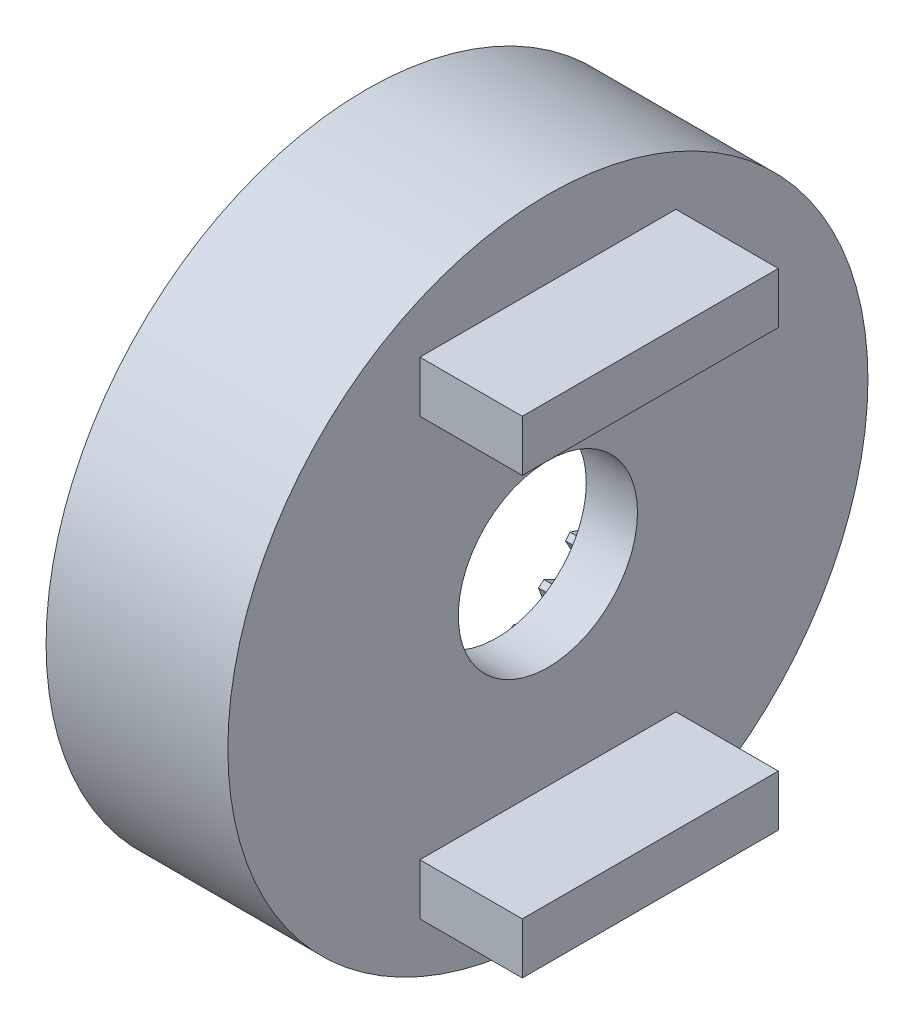
SolidWorks part; units mm, degrees
ref_plane "Plane1" through (0, 0, 0) normal (0, 0, 1) x (1, 0, 0)
ref_plane "Plane2" through (0, 0, 0) normal (0, 1, 0) x (1, 0, 0)
ref_plane "Plane3" through (0, 0, 0) normal (1, 0, 0) x (0, 0, -1)
other "Configuration Table"
sketch "HoldingSke" plane through (0, 0, 0) normal (0, 1, 0) x (1, 0, 0)
  line L0 (0, 0) -> (1.4627, -1.364)
  line L1 (-15, 0) -> (100, 0) construction
  line L2 (0, 0) -> (-2.1039, 2.3779)
  line L3 (0, 0) -> (-11.863, 4.5341)
  line L4 (0, 0) -> (6.316, 5.8897)
  line L5 (0, 0) -> (-23.7986, -8.8762)
  line L6 (0, 0) -> (-10.5278, -7.1032)
  line L7 (-2.1039, 2.3779) -> (3.3635, 27.1825)
  line L8 (-76.2, 2.8779) -> (-54.61, 2.8779)
  line L9 (-71.009, 38.7566) -> (-53.1078, 45.2721)
  line L10 (-76.2, 71.12) -> (104.1128, 71.12)
  line L11 (0, 0) -> (-2, 0)
  line L12 (-76.2, 101.6) -> (-76.181, 101.6)
  line L13 (24.9733, 27.94) -> (52.9518, 28.4284)
  line L14 (24.9733, 27.94) -> (24.9743, 27.94)
  line L15 (24.9733, 27.94) -> (100.4006, 29.5858)
  circle A0 centre (0, 0) radius 12.5
  circle A1 centre (0, 0) radius 12.7
  circle A2 centre (0, 0) radius 12.7
  dimension "Num_teeth" = 43
  dimension "Pitch_radius" = 180.3128
  dimension "Width" = 2
  dimension "Diameter" = 25
sketch "BasProSke" plane through (0, 0, 0) normal (0, 1, 0) x (1, 0, 0)
  line L0 (-10, 0) -> (60, 0) construction
  line L1 (0, 10.25) -> (0, 12.5)
  line L2 (0, 10.25) -> (5.1, 10.25)
  line L3 (5.1, 10.25) -> (5.1, 12.5)
  line L4 (5.1, 12.5) -> (0, 12.5)
  dimension "Thickness" = 5.1
  dimension "Diameter" = 25
revolve "Base-Revolve" add sketch "BasProSke" angle 360 about L0
sketch "TooCutSke" plane through (0, 0, 0) normal (1, 0, 0) x (0, 0, -1)
  line L3 (0.4401, 10.741) -> (0.4401, 53.6633) construction
  line L4 (0, 0) -> (0, 59.563) construction
  line L5 (0, 0) -> (-4.9876, 68.1452) construction
  line L6 (-4.5651, 8.7817) -> (37.0782, 11.8296) construction
  circle A0 centre (0, 0) radius 10.75 construction
  circle A1 centre (0, 0) radius 11.376 construction
  circle A2 centre (0, 0) radius 9.0915 construction
  circle A3 centre (0, 0) radius 10.2246 construction
  arc A4 (0.6178, 10.2059) -> (0.1429, 11.3751) centre (-4.5651, 8.7817) ccw
  arc A5 (0.6178, 10.2059) -> (-0.6178, 10.2059) centre (0, 0) ccw
  arc A6 (0.1429, 11.3751) -> (-0.1429, 11.3751) centre (0, 0) ccw
  arc A7 (-0.1429, 11.3751) -> (-0.6178, 10.2059) centre (4.5651, 8.7817) ccw
extrude "ToothCut" cut sketch "TooCutSke" along normal through all
fillet "Breaks" [suppressed] radius 0.05
fillet "RootFillets" [suppressed] radius 0.126
pattern_circular "TeethCuts" count 43 over 360 about axis through (-10, 0, 0) along (1, 0, 0) of "RootFillets", "Breaks", "ToothCut"
sketch "草图1" plane through (5.1, 0, 0) normal (1, 0, 0) x (0, 0, -1)
  line L1 (-5, 9.5) -> (5, 9.5)
  line L2 (-5, 9.5) -> (-5, 7.5)
  line L3 (-5, 7.5) -> (5, 7.5)
  line L4 (5, 9.5) -> (5, 7.5)
  line L5 (-5, -7.5) -> (5, -7.5)
  line L6 (-5, -7.5) -> (-5, -9.5)
  line L7 (-5, -9.5) -> (5, -9.5)
  line L8 (5, -7.5) -> (5, -9.5)
  circle A0 centre (0, 0) radius 12.5
  circle A1 centre (0, 0) radius 3.5
  circle A2 centre (0, 0) radius 7.5 construction
  point P13 (0, 7.5)
  point P14 (0, -7.5)
  dimension "D1" = 25
  dimension "D2" = 7
  dimension "D3" = 15
  dimension "D4" = 2
  dimension "D6" = 10
extrude "凸台-拉伸1" add sketch "草图1" along normal blind 2 contours A0 | A1
extrude "凸台-拉伸2" add sketch "草图1<3>" along normal blind 4 from surface contours L4 L1 L2 L3 | L8 L5 L6 L7 region at (5.1, 8.5, 0) region at (5.1, -8.5, 0) starting at face at (7.1, 0, -12.5)
sketch "草图1<3>" plane through (5.1, 0, 0) normal (1, 0, 0) x (0, 0, -1) same geometry as "草图1"
equation "' \"Module@HoldingSke\" = 6.35"
equation "' \"Num_teeth@HoldingSke\" = 24"
equation "' \"Ap@HoldingSke\" =  14.5"
equation "' \"Ap@HoldingSke\" = 14.5"
equation "' \"Width@HoldingSke\" = 12"
equation "' \"Diameter@HoldingSke\" = 8 * 25.4"
equation "' \"Show_teeth@HoldingSke\" = 100"
equation "' \"Backlash@HoldingSke\" = 0.009 * 25.4"
equation "' \"Addendum_fac@HoldingSke\" = 1.0"
equation "' \"Dedendum_fac@HoldingSke\" = 1.25"
equation "' \"Dedendum_add@HoldingSke\" = 0.00005 * 25.4"
equation "' \"Clearance_fac@HoldingSke\" = 0.25"
equation "\"Pitch@HoldingSke\" = 1 / \"Module@HoldingSke\" "
equation "\"Overcut_dia@TooCutSke\" = (\"Num_teeth@HoldingSke\" - 2 * \"Addendum_fac@HoldingSke\") / \"Pitch@HoldingSke\" - 0.002 * 25.4"
equation "\"Pitch_dia@TooCutSke\" = \"Num_teeth@HoldingSke\" / \"Pitch@HoldingSke\""
equation "\"Base_dia@TooCutSke\" = \"Num_teeth@HoldingSke\" / \"Pitch@HoldingSke\" * cos((\"Ap@HoldingSke\"  * 3.14159265 / 180)) * 0.90"
equation "\"Root_dia@TooCutSke\" = \"Num_teeth@HoldingSke\"  / \"Pitch@HoldingSke\" + 2 *  \"Dedendum_fac@HoldingSke\"/ \"Pitch@HoldingSke\" + \"Dedendum_add@HoldingSke\" * 2"
equation "\"Half_ang@TooCutSke\" = 180 / \"Num_teeth@HoldingSke\""
equation "\"Half_CT@TooCutSke\" = \"Num_teeth@HoldingSke\" / \"Pitch@HoldingSke\" * sin((3.14159265 / 2 / \"Num_teeth@HoldingSke\")) / 2 + 10 * \"Backlash@HoldingSke\" / 4"
equation "\"Flank_rad@TooCutSke\" = \"Num_teeth@HoldingSke\" / \"Pitch@HoldingSke\" / 4"
equation "\"Radius@RootFillets\"= \"Clearance_fac@HoldingSke\" / \"Pitch@HoldingSke\" + \"Dedendum_add@HoldingSke\""
equation "\"Break_rad@Breaks\" = 0.02 / \"Pitch@HoldingSke\" * 5"
equation "\"Num_teeth@TeethCuts\" = int( \"Show_teeth@HoldingSke\" ) + 1"
equation "\"Num_teeth@TeethCuts\" = ((sgn( \"Num_teeth@TeethCuts\" - \"Num_teeth@HoldingSke\" )-1)*( \"Num_teeth@TeethCuts\" - \"Num_teeth@HoldingSke\" ))/-2+ \"Num_teeth@HoldingSke\""
equation "\"Num_teeth@TeethCuts\" = ((sgn( \"Num_teeth@TeethCuts\" - 2.0)+1)*( \"Num_teeth@TeethCuts\" - 2.0))/2 +2.0"
equation "\"Angle@TeethCuts\" = 360.0 / \"Num_teeth@HoldingSke\""
equation "\"Diameter@BasProSke\" = \"Num_teeth@HoldingSke\"  / \"Pitch@HoldingSke\" + 2 *  \"Dedendum_fac@HoldingSke\"/ \"Pitch@HoldingSke\" + \"Dedendum_add@HoldingSke\" * 2 + 0.002 * 25.4"
equation "\"Diameter@BasProSke\" = ((sgn( \"Diameter@BasProSke\"  - \"Diameter@HoldingSke\" )+1)*( \"Diameter@BasProSke\"  - \"Diameter@HoldingSke\" ))/2 + \"Diameter@HoldingSke\""
equation "\"Inside_diameter@BasProSke\" =  (\"Num_teeth@HoldingSke\" - 2 * \"Addendum_fac@HoldingSke\") / \"Pitch@HoldingSke\" "
